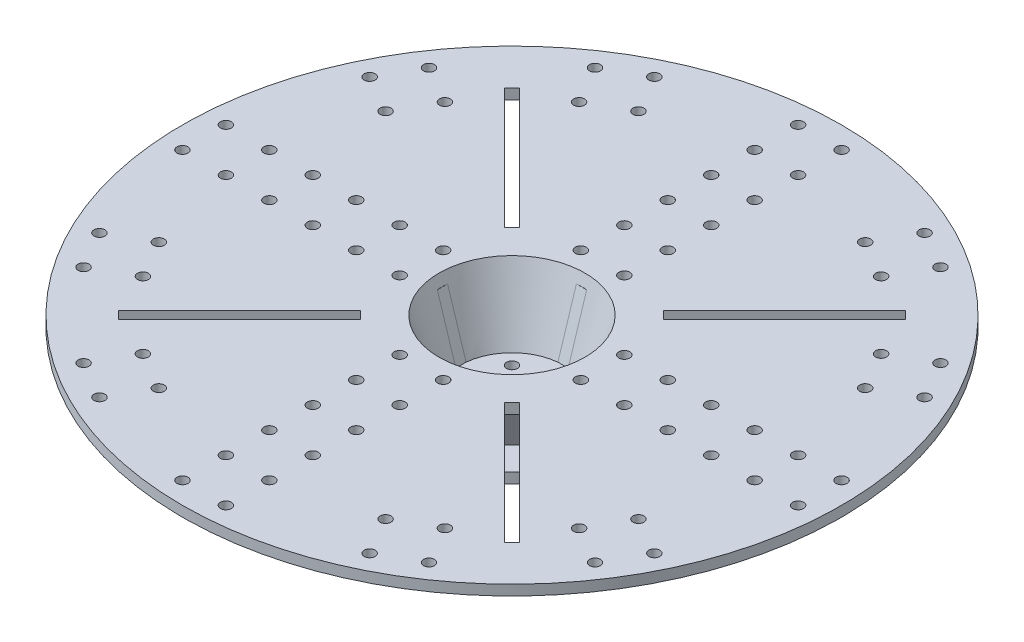
SolidWorks part; units mm, degrees
note: '?' marks a value the reader was unsure of.
material "ULTEM 9085"
ref_plane "Front Plane" through (0, 0, 0) normal (0, 0, 1) x (1, 0, 0)
ref_plane "Top Plane" through (0, 0, 0) normal (0, 1, 0) x (1, 0, 0)
ref_plane "Right Plane" through (0, 0, 0) normal (1, 0, 0) x (0, 0, -1)
other "Center of Mass"
sketch "Sketch1" plane through (0, 0, 0) normal (0, 0, 1) x (1, 0, 0)
  line L0 (0, -40.25) -> (0, -46.25)
  line L1 (0, -40.25) -> (30, -40.25)
  line L2 (30, -40.25) -> (42.6498, 0)
  line L3 (42.6498, 0) -> (192.6498, 0)
  line L4 (94.9574, 0) -> (-94.9574, 0) construction
  line L5 (192.6498, 0) -> (192.6498, -6)
  line L6 (42.6498, 0) -> (42.6498, -31.4331) construction
  line L7 (192.6498, -6) -> (46.8968, -6)
  line L8 (36.1179, -40.2971) -> (46.8968, -6)
  line L9 (36.1179, -40.2971) -> (55.5, -40.2971)
  line L10 (55.5, -40.2971) -> (55.5, -46.25)
  line L11 (55.5, -46.25) -> (0, -46.25)
  line L12 (0, -25.4375) -> (0, 25.4375) construction
  point P15 (0, -43.25)
  point P16 (55.5, -43.2736)
  point P24 (36.3249, -20.125)
  point P25 (41.5074, -23.1486)
  dimension "D1" = 72.553
  dimension "D2" = 30
  dimension "D3" = 150
  dimension "D4" = 6
  dimension "D5" = 6
  dimension "D6" = 55.5
  dimension "D7" = 34.2971
  dimension "D8" = 40.25
  dimension "D9" = 6
revolve "Revolve2" add sketch "Sketch1" angle 360 about L0
ref_axis "Axis1" through (0, 0, 0) along (0, -1, 0)?
sketch "Sketch3" plane through (0, 0, 0) normal (0, 0, 1) x (1, 0, 0)
  line L0 (55.5, -40.2971) -> (192.6498, -6)
  line L1 (192.6498, -6) -> (0, -6)
  line L2 (-192.6498, -6) -> (192.6498, -6) construction
  line L3 (0, -6) -> (0, -40.2971)
  line L4 (55.5, -40.2971) -> (-55.5, -40.2971) construction
  line L5 (0, -40.2971) -> (55.5, -40.2971)
extrude "Boss-Extrude2" add sketch "Sketch3" along normal mid plane 6
pattern_circular "CirPattern2" count 4 over 360 about axis through (0, 0, 0) along (0, 1, 0) of "Boss-Extrude2"
sketch "Sketch6" plane through (0, 0, 3) normal (0, 0, 1) x (1, 0, 0)
  line L0 (-3, -6) -> (-40.6536, -6)
  line L1 (-40.6536, -6) -> (-29.8496, -40.25)
  line L2 (-29.8496, -40.25) -> (-3, -40.25)
  line L3 (-3, -40.25) -> (-3, -6)
  spline S0 degree 3 poles (-29.8496, -40.25) (-33.4553, -28.8347) (-37.0555, -17.4177) (-40.6536, -6) knots 0 0 0 0 1 1 1 1 construction
extrude "Cut-Extrude3" cut sketch "Sketch6" against normal blind 6
pattern_circular "CirPattern4" count 4 over 360 about axis through (0, 0, 0) along (0, 1, 0) of "Cut-Extrude3"
sketch "Sketch7" plane through (0, -6, 0) normal (0, 1, 0) x (1, 0, 0)
  line L0 (-3, 3) -> (-3, -3)
  line L1 (-3, -3) -> (3, -3)
  line L2 (-3, -3) -> (3, -3) construction
  line L3 (3, -3) -> (3, 3)
  line L4 (3, 3) -> (-3, 3) construction
  line L5 (3, 3) -> (-3, 3)
extrude "Cut-Extrude4" cut sketch "Sketch7" against normal up to surface (34.25 mm away) up to face at (0, -40.25, 0)
sketch "Sketch8" plane through (0, -40.25, 0) normal (0, 1, 0) x (1, 0, 0)
  circle A0 centre (0, 0) radius 3.175
  dimension "D1" = 6.35
extrude "Cut-Extrude5" cut sketch "Sketch8" against normal through all
sketch "Sketch11" plane through (0, -6, 0) normal (0, -1, 0) x (1, 0, 0)
  line L0 (0, -25.4375) -> (0, 25.4375) construction
  circle A0 centre (-12.7, 179.9498) radius 3.2
  arc A2 (3, 192.6264) -> (0, 192.6498) centre (0, 0) ccw construction
  point P9 (0, 192.6498)
  dimension "D1" = 6.4
  dimension "D2" = 12.7
  dimension "D3" = 12.7
extrude "Cut-Extrude6" cut sketch "Sketch11" against normal through all
pattern_linear "LPattern2" count 2 spacing 25.4 along (1, 0, 0) count 6 spacing 25.4 along (0, 0, -1) of "Cut-Extrude6"
pattern_circular "CirPattern5" count 4 over 360 about axis through (0, 0, 0) along (0, 1, 0) of "LPattern2", "Cut-Extrude6"
sketch "Sketch12" plane through (0, 0, 0) normal (0, 1, 0) x (1, 0, 0)
  line L0 (0, 0) -> (-166.8396, -96.3249) construction
  line L1 (-25.4375, 0) -> (25.4375, 0) construction
  circle A0 centre (0, 0) radius 192.6498 construction
  dimension "D1" = 30
sketch "Sketch13" plane through (0, 0, 0) normal (0, 1, 0) x (1, 0, 0)
  line L0 (0, 0) -> (166.8396, -96.3249) construction
  line L1 (-25.4375, 0) -> (25.4375, 0) construction
  circle A0 centre (0, 0) radius 192.6498 construction
  dimension "D1" = 30
sketch "Sketch15" plane through (0, 0, 0) normal (0, 1, 0) x (1, 0, 0)
  line L0 (166.8396, -96.3249) -> (133.0574, -154.8374) construction
  line L1 (0, 0) -> (166.8396, -96.3249) construction
  dimension "D1" = 90
sketch "Sketch17" plane through (0, 0, 0) normal (0, 1, 0) x (1, 0, 0)
  line L0 (0, 0) -> (166.8396, -96.3249) construction
  line L1 (166.8396, -96.3249) -> (133.0574, -154.8374) construction
  circle A0 centre (149.4911, -100.9734) radius 3.2
  dimension "D1" = 6.4
  dimension "D2" = 12.7
  dimension "D3" = 12.7
extrude "Cut-Extrude7" cut sketch "Sketch17" against normal through all
pattern_linear "LPattern3" count 2 spacing 25.4 along (-0.866, 0, -0.5) count 2 spacing 25.4 along (0.5, 0, -0.866) of "Cut-Extrude7"
mirror "Mirror1" about plane through (0, 0, 0) normal (1, 0, 0) of "LPattern3", "Cut-Extrude7"
mirror "Mirror2" about plane through (0, 0, 0) normal (0, 0, 1) of "Mirror1", "Cut-Extrude7", "LPattern3"
sketch "Sketch18" plane through (0, 0, 0) normal (0, 1, 0) x (1, 0, 0)
  line L0 (0, 0) -> (136.224, 136.224) construction
  line L1 (-25.4375, 0) -> (25.4375, 0) construction
  circle A0 centre (0, 0) radius 192.6498 construction
  dimension "D1" = 45
sketch "Sketch19" plane through (0, 0, 0) normal (0, 1, 0) x (1, 0, 0)
  line L0 (117.2735, 112.748) -> (112.748, 117.2735)
  line L1 (117.2735, 112.748) -> (46.5628, 42.0374)
  line L2 (112.748, 117.2735) -> (42.0374, 46.5628)
  line L3 (46.5628, 42.0374) -> (42.0374, 46.5628)
  line L5 (0, 0) -> (136.224, 136.224) construction
  point P6 (115.0108, 115.0108)
  dimension "D1" = 3.2
  dimension "D2" = 6.4
  dimension "D3" = 100
  dimension "D4" = 30
extrude "Cut-Extrude8" cut sketch "Sketch19" against normal up to next
pattern_circular "CirPattern6" count 4 over 360 about axis through (0, 0, 0) along (0, 1, 0) of "Cut-Extrude8"
sketch "Sketch23" plane through (0, -46.25, 0) normal (0, -1, 0) x (1, 0, 0)
  line L0 (23, -39.8372) -> (0, 0) construction
  line L1 (0, -25.4375) -> (0, 25.4375) construction
  circle A0 centre (23, -39.8372) radius 3.2
  dimension "D1" = 6.4
  dimension "D3" = 30
  dimension "D2" = 46
extrude "Cut-Extrude9" cut sketch "Sketch23" along direction (0, 1, 0) on the side against the normal up to next (5.9529 mm away)
pattern_circular "CirPattern7" count 2 every 30 about axis through (0, 0, 0) along (0, -1, 0) of "Cut-Extrude9"
pattern_circular "CirPattern8" count 4 over 360 about axis through (0, 0, 0) along (0, 1, 0) of "CirPattern7", "Cut-Extrude9"
sketch "Sketch24" plane through (0, 0, 0) normal (0, 1, 0) x (1, 0, 0)
  line L0 (96.3249, -166.8396) -> (0, 0) construction
  line L1 (0, -25.4375) -> (0, 25.4375) construction
  circle A0 centre (0, 0) radius 192.6498 construction
  dimension "D1" = 30
sketch "Sketch25" plane through (0, 0, 0) normal (0, 1, 0) x (1, 0, 0)
  line L0 (96.3249, -166.8396) -> (64.8663, -185.0022) construction
  line L1 (96.3249, -166.8396) -> (0, 0) construction
  dimension "D1" = 90
sketch "Sketch26" plane through (0, 0, 0) normal (0, 1, 0) x (1, 0, 0)
  line L0 (96.3249, -166.8396) -> (64.8663, -185.0022) construction
  line L1 (96.3249, -166.8396) -> (0, 0) construction
  circle A0 centre (78.9764, -162.1911) radius 3.2
  dimension "D1" = 6.4
  dimension "D2" = 12.7
  dimension "D3" = 12.7
extrude "Cut-Extrude10" cut sketch "Sketch26" against normal through all
pattern_linear "LPattern4" count 2 spacing 25.4 along (-0.5, 0, -0.866) count 2 spacing 25.4 along (0.866, 0, -0.5) of "Cut-Extrude10"
mirror "Mirror3" about plane through (0, 0, 0) normal (1, 0, 0) of "LPattern4", "Cut-Extrude10"
mirror "Mirror4" about plane through (0, 0, 0) normal (0, 0, 1) of "Mirror3", "Cut-Extrude10", "LPattern4"
sketch "Sketch27" plane through (0, -46.25, 0) normal (0, -1, 0) x (1, 0, 0)
  line L0 (0, 0) -> (136.224, -136.224) construction
  circle A0 centre (14.8492, -14.8492) radius 3.2
  dimension "D1" = 6.4
  dimension "D2" = 21
extrude "Cut-Extrude11" cut sketch "Sketch27" against normal up to next
pattern_circular "CirPattern9" count 4 over 360 about axis through (0, 0, 0) along (0, 1, 0) of "Cut-Extrude11"
sketch "Sketch28" plane through (3, 0, 0) normal (1, 0, 0) x (0, 0, -1)
  line L0 (0, 25.4375) -> (0, -25.4375) construction
  line L1 (51, -12.4) -> (107, -12.4)
  line L2 (51, -12.4) -> (51, -18.8)
  line L3 (51, -18.8) -> (107, -18.8)
  line L4 (107, -12.4) -> (107, -18.8)
  line L5 (3, -6) -> (192.6264, -6) construction
  dimension "D1" = 6.4
  dimension "D2" = 51
  dimension "D3" = 6.4
  dimension "D4" = 56
extrude "Cut-Extrude12" cut sketch "Sketch28" against normal up to next
pattern_circular "CirPattern10" count 4 over 360 about axis through (0, 0, 0) along (0, 1, 0) of "Cut-Extrude12"
